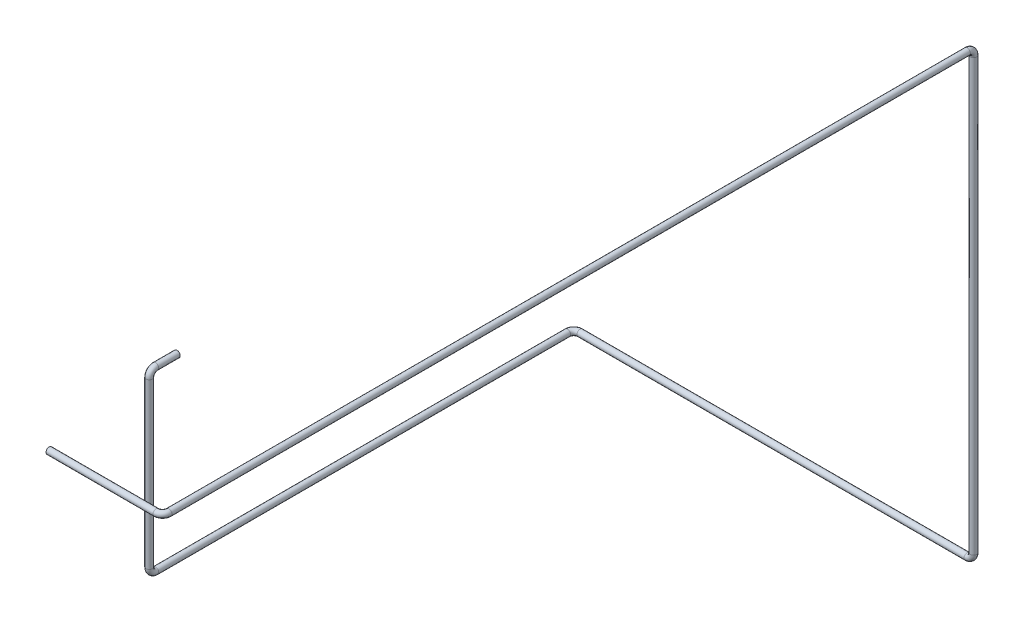
SolidWorks part; units mm, degrees
ref_plane "Plano frontal" through (0, 0, 0) normal (0, 0, 1) x (1, 0, 0)
ref_plane "Plano superior" through (0, 0, 0) normal (0, 1, 0) x (1, 0, 0)
ref_plane "Plano direito" through (0, 0, 0) normal (1, 0, 0) x (0, 0, -1)
sketch3d "3DSketch1"
  line L0 (-29691.5162, -14997.0136, 42998.3902) -> (-29185.3, -14997.0136, 42998.3902)
  line L1 (-29155.3, -14997.0136, 42968.3902) -> (-29155.3, -14997.0136, 39192.6412)
  line L2 (-29691.5162, -14997.0136, 42998.3902) -> (-29699.8896, -14997.0136, 42998.3902) construction
  line L3 (-29695.7273, -14997.0136, 42998.3902) -> (-29721.2483, -14997.0136, 42998.3902) construction
  line L4 (-29155.3, -15027.0136, 39162.6412) -> (-29155.3, -17064.6661, 39162.6412)
  line L5 (-29185.3, -17094.6661, 39162.6412) -> (-31016.0335, -17094.6661, 39162.6412)
  line L6 (-31046.0335, -17094.6661, 39192.6412) -> (-31046.0335, -17094.6661, 41140.6368)
  line L7 (-31046.0335, -17064.6661, 41170.6368) -> (-31046.0335, -16287.8595, 41170.6368)
  line L8 (-31046.0335, -16257.8595, 41140.6368) -> (-31046.0335, -16257.8595, 41039.2367)
  line L9 (-31046.0335, -16257.8595, 41013.2907) -> (-31046.0335, -16257.8595, 41039.2367) construction
  line L10 (-31046.0335, -16257.8595, 41013.2907) -> (-31046.0335, -16257.8595, 40878.7861) construction
  line L11 (-31046.0335, -16257.8595, 40957.8552) -> (-31046.0335, -16257.8595, 41013.2907) construction
  arc A1 (-31046.0335, -16257.8595, 41140.6368) -> (-31046.0335, -16287.8595, 41170.6368) centre (-31046.0335, -16287.8595, 41140.6368) ccw
  arc A2 (-31046.0335, -17064.6661, 41170.6368) -> (-31046.0335, -17094.6661, 41140.6368) centre (-31046.0335, -17064.6661, 41140.6368) ccw
  arc A3 (-31046.0335, -17094.6661, 39192.6412) -> (-31016.0335, -17094.6661, 39162.6412) centre (-31016.0335, -17094.6661, 39192.6412) ccw
  arc A4 (-29185.3, -17094.6661, 39162.6412) -> (-29155.3, -17064.6661, 39162.6412) centre (-29185.3, -17064.6661, 39162.6412) ccw
  arc A5 (-29155.3, -15027.0136, 39162.6412) -> (-29155.3, -14997.0136, 39192.6412) centre (-29155.3, -15027.0136, 39192.6412) ccw
  arc A6 (-29155.3, -14997.0136, 42968.3902) -> (-29185.3, -14997.0136, 42998.3902) centre (-29185.3, -14997.0136, 42968.3902) ccw
  point P12 (-31046.0335, -17393.736, 39165.1444)
  point P17 (-31046.0335, -16257.8595, 41039.2367)
  point P18 (-31046.0335, -17224.5739, 41170.6368)
  point P21 (-31046.0335, -16257.8595, 41170.6368)
  point P22 (-31016.0335, -16287.8595, 41140.6368)
  point P25 (-31046.0335, -17094.6661, 41170.6368)
  point P26 (-31016.0335, -17064.6661, 41140.6368)
  point P29 (-31046.0335, -17094.6661, 39162.6412)
  point P30 (-31016.0335, -17124.6661, 39192.6412)
  point P33 (-29155.3, -17094.6661, 39162.6412)
  point P34 (-29185.3, -17064.6661, 39192.6412)
  point P37 (-29155.3, -14997.0136, 39162.6412)
  point P38 (-29125.3, -15027.0136, 39192.6412)
  point P41 (-29155.3, -14997.0136, 42998.3902)
  point P42 (-29185.3, -15027.0136, 42968.3902)
  dimension "D1" = 30
sweep "Sweep-Thin1" add path "3DSketch1" circular profile diameter 30 parameters "D1"=1, "D3"=30
